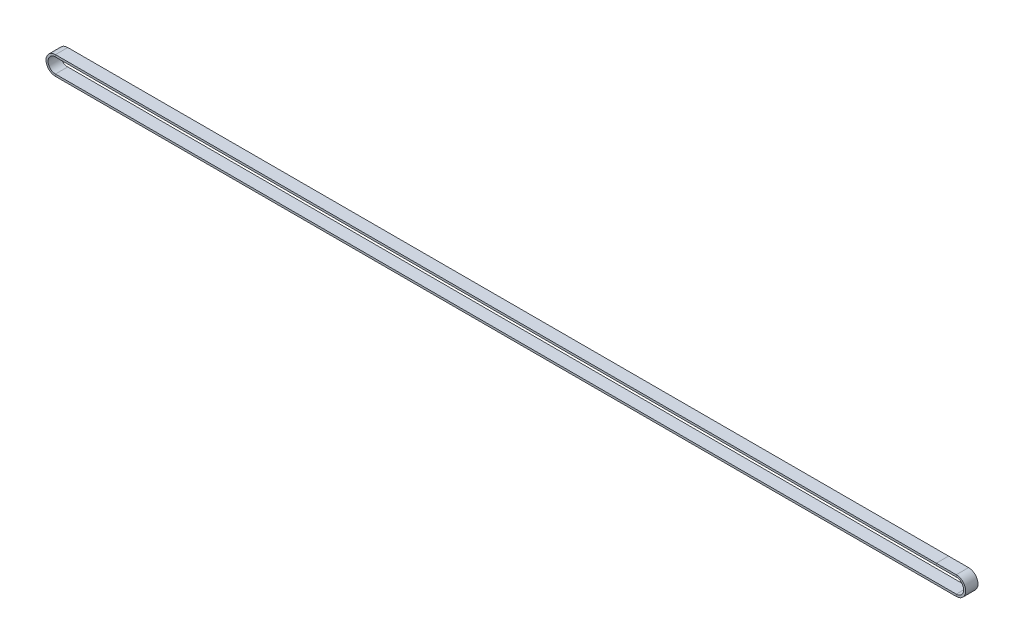
SolidWorks part; units mm, degrees
ref_plane "Front Plane" through (0, 0, 0) normal (0, 0, 1) x (1, 0, 0)
ref_plane "Top Plane" through (0, 0, 0) normal (0, 1, 0) x (1, 0, 0)
ref_plane "Right Plane" through (0, 0, 0) normal (1, 0, 0) x (0, 0, -1)
ref_plane "Plane1" through (-16, 0, 0) normal (1, 0, 0) x (0, 0, -1)
sketch "Sketch2" plane through (0, 0, 0) normal (0, 0, 1) x (1, 0, 0)
  line L0 (0, 0) -> (1, 0) construction
  line L1 (0, 0) -> (0, 1) construction
  line L2 (-1.4, -6.9) -> (-660.3327, -6.9)
  line L3 (-660.3327, 6.9) -> (-1.4, 6.9)
  arc A0 (-1.4, 6.9) -> (-1.4, -6.9) centre (-1.4, 0) cw
  arc A1 (-660.3327, -6.9) -> (-660.3327, 6.9) centre (-660.3327, 0) cw
sketch "Sketch3" plane through (-16, 0, 0) normal (1, 0, 0) x (0, 0, -1)
  line L1 (0, 6.9) -> (-9, 6.9)
  line L2 (0, 6.9) -> (0, 5.4)
  line L3 (0, 5.4) -> (-9, 5.4)
  line L4 (-9, 6.9) -> (-9, 5.4)
  point P4 (0, 0)
  point P5 (0, 0)
  point P6 (0, 0)
  dimension "D1" = 1.5
  dimension "D2" = 9
sweep "Sweep1" add profiles "Sketch3" path "Sketch2"
move or copy body "Body-Move/Copy1" [suppressed] bodies to move or copy 101
